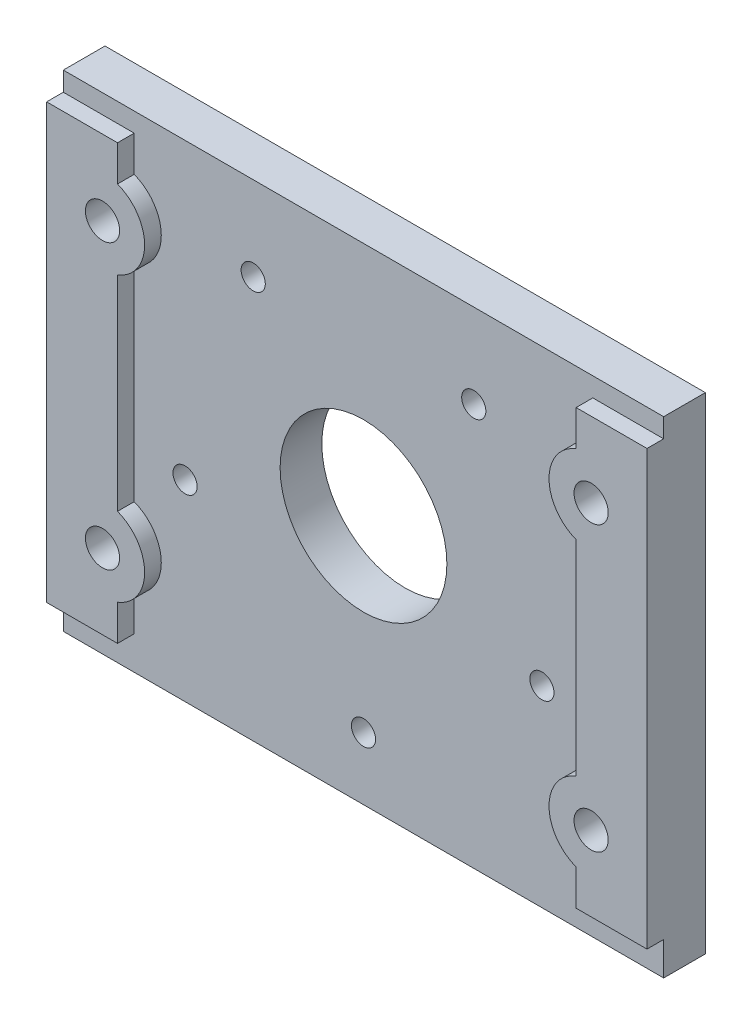
SolidWorks part; units mm, degrees
ref_plane "Front Plane" through (0, 0, 0) normal (0, 0, 1) x (1, 0, 0)
ref_plane "Top Plane" through (0, 0, 0) normal (0, 1, 0) x (1, 0, 0)
ref_plane "Right Plane" through (0, 0, 0) normal (1, 0, 0) x (0, 0, -1)
ref_plane "Plane1" through (0, 0, 280) normal (0, 0, 1) x (1, 0, 0)
sketch "Sketch1" plane through (0, 0, 280) normal (0, 0, 1) x (1, 0, 0)
  line L0 (264, 270) -> (336, 270)
  line L1 (336, 270) -> (336, 328.3)
  line L2 (336, 328.3) -> (264, 328.3)
  line L3 (264, 328.3) -> (264, 270)
  circle A0 centre (300, 300) radius 10
  circle A1 centre (286.7748, 318.2029) radius 1.45
  circle A2 centre (278.6012, 293.0471) radius 1.45
  circle A3 centre (300, 277.5) radius 1.45
  circle A4 centre (321.3988, 293.0471) radius 1.45
  circle A5 centre (313.2252, 318.2029) radius 1.45
extrude "Boss-Extrude1" add sketch "Sketch1" along normal blind 5
sketch "Sketch2" plane through (0, 0, 280) normal (0, 0, 1) x (1, 0, 0)
  line L0 (264, 274) -> (272.5, 274)
  line L1 (272.5, 274) -> (272.5, 326)
  line L2 (272.5, 326) -> (264, 326)
  line L3 (264, 326) -> (264, 274)
extrude "Boss-Extrude2" add sketch "Sketch2" along normal blind 7
sketch "Sketch3" plane through (0, 0, 280) normal (0, 0, 1) x (1, 0, 0)
  circle A0 centre (270.7, 283) radius 5.05
extrude "Boss-Extrude3" add sketch "Sketch3" along normal blind 7
sketch "Sketch4" plane through (0, 0, 280) normal (0, 0, 1) x (1, 0, 0)
  circle A0 centre (270.7, 317) radius 5.05
extrude "Boss-Extrude4" add sketch "Sketch4" along normal blind 7
ref_plane "Plane2" through (0, 0, 280.3) normal (0, 0, 1) x (1, 0, 0)
sketch "Sketch5" plane through (0, 0, 280.3) normal (0, 0, 1) x (1, 0, 0)
  circle A0 centre (270.7, 283) radius 2.05
  circle A1 centre (270.7, 317) radius 2.05
extrude "Cut-Extrude1" cut sketch "Sketch5" along normal blind 6.7
sketch "Sketch6" plane through (0, 0, 280) normal (0, 0, 1) x (1, 0, 0)
  line L0 (327.5, 274) -> (336, 274)
  line L1 (336, 274) -> (336, 326)
  line L2 (336, 326) -> (327.5, 326)
  line L3 (327.5, 326) -> (327.5, 274)
extrude "Boss-Extrude5" add sketch "Sketch6" along normal blind 7
sketch "Sketch7" plane through (0, 0, 280) normal (0, 0, 1) x (1, 0, 0)
  circle A0 centre (329.3, 283) radius 5.05
extrude "Boss-Extrude6" add sketch "Sketch7" along normal blind 7
sketch "Sketch8" plane through (0, 0, 280) normal (0, 0, 1) x (1, 0, 0)
  circle A0 centre (329.3, 317) radius 5.05
extrude "Boss-Extrude7" add sketch "Sketch8" along normal blind 7
sketch "Sketch9" plane through (0, 0, 280.3) normal (0, 0, 1) x (1, 0, 0)
  circle A0 centre (329.3, 283) radius 2.05
  circle A1 centre (329.3, 317) radius 2.05
extrude "Cut-Extrude2" cut sketch "Sketch9" along normal blind 6.7
ref_plane "Plane3" through (300, 0, 0) normal (1, 0, 0) x (0, 0, -1)
ref_plane "Plane4" through (0, 300, 0) normal (0, 1, 0) x (1, 0, 0)
ref_axis "HIP_AXIS" through (300, 300, 287.35) along (0, 0, -1)
ref_plane "Plane5" through (0, 0, 300) normal (0, 0, 1) x (1, 0, 0)
ref_axis "ABAD_AXIS" through (339.6, 300, 300) along (-1, 0, 0)
